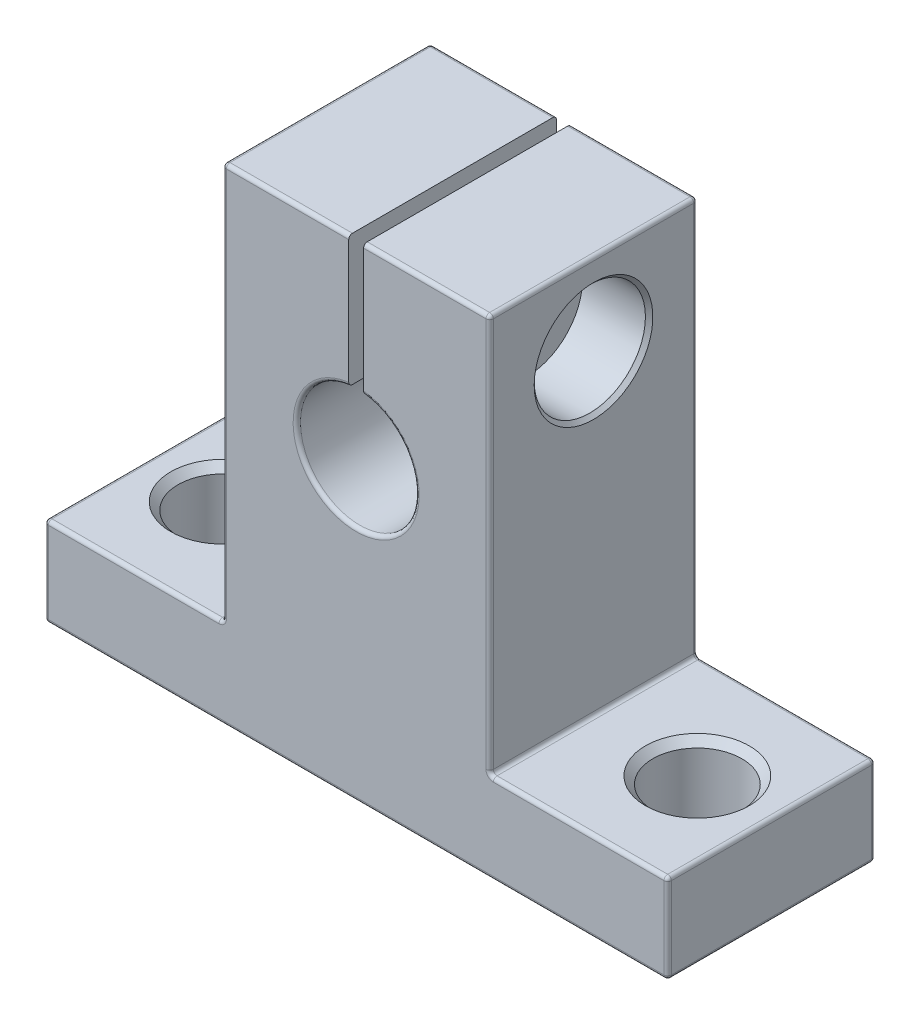
SolidWorks part; units mm, degrees
ref_plane "Ön Düzlem" through (0, 0, 0) normal (0, 0, 1) x (1, 0, 0)
ref_plane "Üst Düzlem" through (0, 0, 0) normal (0, 1, 0) x (1, 0, 0)
ref_plane "Sağ Düzlem" through (0, 0, 0) normal (1, 0, 0) x (0, 0, -1)
sketch "Sketch1" plane through (0, 0, 0) normal (0, 0, 1) x (1, 0, 0)
  line L0 (0, 0) -> (0, 6)
  line L1 (0, 6) -> (-12, 6)
  line L2 (-12, 6) -> (-12, 32.8)
  line L3 (-12, 32.8) -> (-20.5, 32.8)
  line L4 (-30, 32.8) -> (-30, 6)
  line L5 (-30, 6) -> (-42, 6)
  line L6 (-42, 6) -> (-42, 0)
  line L7 (-42, 0) -> (0, 0)
  line L8 (-36.3388, 16) -> (-4.0454, 16) construction
  line L9 (-21, 12.597) -> (-21, -8.2832) construction
  line L10 (-20.5, 32.8) -> (-20.5, 23.9686)
  line L11 (-21.5, 32.8) -> (-21.5, 23.9686)
  line L12 (-21.5, 32.8) -> (-30, 32.8)
  arc A0 (-21.5, 23.9686) -> (-20.5, 23.9686) centre (-21, 20) ccw
  dimension "D6" = 8
  dimension "D1" = 6
  dimension "D2" = 26.8
  dimension "D3" = 18
  dimension "D4" = 42
  dimension "D5" = 16
  dimension "D7" = 1
extrude "Boss-Extrude1" add sketch "Sketch1" along normal blind 14
sketch "Sketch2" plane through (0, 6, 0) normal (0, 1, 0) x (1, 0, 0)
  line L0 (-40, 3.765) -> (-40, -16.7285) construction
  line L1 (-42, -14) -> (-42, 0) construction
  line L2 (-2, 2.3516) -> (-2, -17.0583) construction
  line L3 (0, -14) -> (0, 0) construction
  line L6 (-46.5344, -7) -> (3.3567, -7) construction
  line L7 (-30, 0) -> (-42, 0) construction
  line L8 (-30, -14) -> (-42, -14) construction
  circle A0 centre (-5, -7) radius 3
  circle A1 centre (-37, -7) radius 3
  dimension "D2" = 6
  dimension "D1" = 2
  dimension "D3" = 2
extrude "Cut-Extrude1" cut sketch "Sketch2" against normal up to next
sketch "Sketch5" plane through (-12, 0, 0) normal (1, 0, 0) x (0, 0, -1)
  line L0 (-18.57, 29.3) -> (6.046, 29.3) construction
  line L1 (-14, 32.8) -> (0, 32.8) construction
  line L2 (-7, 33.5169) -> (-7, 17.2332) construction
  line L3 (-14, 6) -> (-14, 32.8) construction
  line L4 (0, 6) -> (0, 32.8) construction
  circle A0 centre (-7, 27.3) radius 2
  dimension "D1" = 4
  dimension "D2" = 3.5
extrude "Cut-Extrude2" cut sketch "Sketch5" against normal blind 32
cosmetic thread "Cosmetic Thread1" parameters "D2"=5
sketch "Sketch6" plane through (-12, 0, 0) normal (1, 0, 0) x (0, 0, -1)
  circle A0 centre (-7, 27.3) radius 3.75
  dimension "D1" = 7.5
extrude "Cut-Extrude3" cut sketch "Sketch6" against normal blind 4.5
chamfer "Chamfer2" distance 0.25 angle 45 1 edges at (-12, 27.3, 3.25)
fillet "Fillet1" radius 0.25 2 edges at (-21, 16, 0) (-21, 16, 14)
fillet "Fillet2" radius 0.25 2 edges at (-5, 0, 10) (-37, 0, 10)
chamfer "Chamfer3" distance 0.5 angle 45 2 edges at (-37, 6, 10) (-5, 6, 10)
chamfer "Chamfer4" distance 0.5 angle 45 1 edges at (-30, 27.3, 5)
fillet "Fillet3" radius 0.25 24 edges at (-30, 6, 7) (-36, 6, 14) (-42, 3, 14) (-42, 6, 7) (-36, 6, 0) (-42, 3, 0) (0, 3, 14) (0, 0, 7) (0, 3, 0) (-21, 0, 0) (-12, 6, 7) (0, 6, 7) (-6, 6, 14) (-6, 6, 0) (-12, 19.4, 0) (-12, 19.4, 14) (-12, 32.8, 7) (-16.25, 32.8, 14) (-25.75, 32.8, 14) (-30, 19.4, 14) (-30, 19.4, 0) (-30, 32.8, 7) (-25.75, 32.8, 0) (-16.25, 32.8, 0)
fillet "Fillet4" radius 0.25 5 edges at (-41.9268, 0.0732, 0.0732) (-42, 0, 7) (-41.9268, 0, 13.9268) (-0.0732, 0.0732, 13.9268) (-21, 0, 14)
